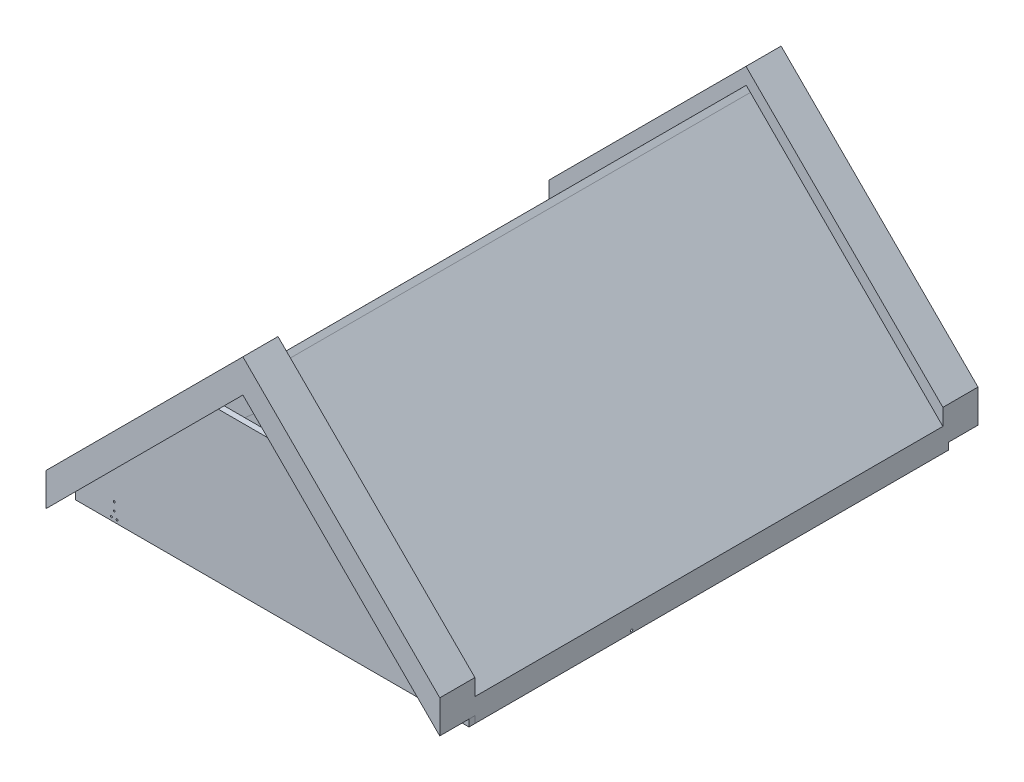
SolidWorks part; units mm, degrees
material "Pine"
ref_plane "Front Plane" through (0, 0, 0) normal (0, 0, 1) x (1, 0, 0)
ref_plane "Top Plane" through (0, 0, 0) normal (0, 1, 0) x (1, 0, 0)
ref_plane "Right Plane" through (0, 0, 0) normal (1, 0, 0) x (0, 0, -1)
sketch "Sketch1" plane through (0, 0, 0) normal (0, 0, 1) x (1, 0, 0)
  line L0 (0, 0) -> (1400, 0)
  line L1 (700, 0) -> (700, 700)
  line L2 (700, 700) -> (0, 0)
  line L3 (700, 700) -> (1400, 0)
  dimension "D1" = 1400
  dimension "D2" = 700
extrude "Boss-Extrude1" add sketch "Sketch1" along normal blind 2000 contours L3 L0 L2
shell "Shell1" thickness 10 removed face at (700, 0, 1000)
sketch "Sketch2" plane through (0, 0, 0) normal (0, -1, 0) x (1, 0, 0)
  line L0 (0, 2000) -> (1400, 2000) construction
  line L1 (-150, 2150) -> (1550, 2150)
  line L2 (-150, 2150) -> (-150, -150)
  line L3 (-150, -150) -> (1550, -150)
  line L4 (1550, 2150) -> (1550, -150)
  line L5 (0, 2000) -> (0, 0) construction
  dimension "D1" = 1700
  dimension "D2" = 2300
  dimension "D3" = 150
  dimension "D4" = 150
sketch "Sketch3" plane through (0, 0, 0) normal (-0.7071, 0.7071, 0) x (0, 0, 1)
  line L10 (2150, 1096.0155) -> (2000, 1096.0155)
  line L11 (2150, 1096.0155) -> (2150, 0)
  line L12 (2150, 0) -> (2000, 0)
  line L13 (2000, 1096.0155) -> (2000, 0)
extrude "Boss-Extrude2" add sketch "Sketch3" along normal blind 100 separate body contours L11 L10 L13 L12
sketch "Sketch7" plane through (700, 700, 0) normal (0.7071, 0.7071, 0) x (0, 0, -1)
  line L5 (-2150, 100) -> (-2000, 100)
  line L6 (-2150, 100) -> (-2150, -989.9495)
  line L7 (-2150, -989.9495) -> (-2000, -989.9495)
  line L8 (-2000, 100) -> (-2000, -989.9495)
extrude "Boss-Extrude4" add sketch "Sketch7" along normal blind 100
sketch "Sketch8" plane through (775, 775, 0) normal (0.7071, 0.7071, 0) x (0, 0, -1)
  line L1 (-2000, 100) -> (-2150, 100)
  line L2 (-2000, 100) -> (-2000, 0)
  line L3 (-2000, 0) -> (-2150, 0)
  line L4 (-2150, 100) -> (-2150, 0)
extrude "Cut-Extrude1" cut sketch "Sketch8" against normal up to vertex (6.066 mm away) and the other way blind 6 up to point (770.7107, 770.7107, 2150)
sketch "Sketch9" plane through (0, 0, 0) normal (-0.7071, -0.7071, 0) x (0, 0, 1)
  line L2 (2000, 100) -> (2150, 100)
  line L3 (2000, 100) -> (2000, 0)
  line L4 (2000, 0) -> (2150, 0)
  line L5 (2150, 100) -> (2150, 0)
extrude "Boss-Extrude5" add sketch "Sketch9" along normal blind 239.05
sketch "Sketch10" plane through (700, -700, 0) normal (0.7071, -0.7071, 0) x (0, 0, -1)
  line L1 (-2000, 989.9495) -> (-2150, 989.9495)
  line L2 (-2000, 989.9495) -> (-2000, 1089.9495)
  line L3 (-2000, 1089.9495) -> (-2150, 1089.9495)
  line L4 (-2150, 989.9495) -> (-2150, 1089.9495)
extrude "Boss-Extrude6" add sketch "Sketch10" along normal blind 399.5
sketch "Sketch13" plane through (0, 0, 2150) normal (0, 0, 1) x (1, 0, 0)
  line L0 (-141.4214, 0) -> (-141.4214, -141.4214)
  line L1 (-150, 0) -> (1550, 0) construction
  line L2 (700, 841.4214) -> (-239.7446, -98.3232) construction
  line L3 (700, 700) -> (-169.0339, -169.0339) construction
  line L4 (-141.4214, -141.4214) -> (-169.0339, -169.0339)
  line L5 (-169.0339, -169.0339) -> (-239.7446, -98.3232)
  line L6 (-239.7446, -98.3232) -> (-141.4214, 0)
  line L7 (1541.4214, 0) -> (1753.1998, -211.7785)
  line L8 (700, 841.4214) -> (1753.1998, -211.7785) construction
  line L9 (1753.1998, -211.7785) -> (1682.4892, -282.4892)
  line L10 (1682.4892, -282.4892) -> (1541.2446, -141.2446)
  line L12 (1541.4214, 0) -> (1541.2446, -141.2446)
extrude "Cut-Extrude4" cut sketch "Sketch13" against normal blind 1197.5
ref_plane "Plane1" through (0, 0, 1000) normal (0, 0, 1) x (1, 0, 0)
mirror "Mirror4" about plane through (0, 0, 1000) normal (0, 0, 1) of bodies 114 108
sketch "Sketch14" plane through (-141.4214, 0, 0) normal (-1, 0, 0) x (0, 0, 1)
  line L0 (0, -141.4214) -> (0, 0) construction
  line L5 (0, -70.7107) -> (2000, -70.7107)
  line L6 (0, -70.7107) -> (0, -170.7107)
  line L7 (0, -170.7107) -> (2000, -170.7107)
  line L8 (2000, -70.7107) -> (2000, -170.7107)
  dimension "D1" = 100
  dimension "D2" = 70.7107
  dimension "D3" = 2000
extrude "Boss-Extrude7" add sketch "Sketch14" against normal blind 25
sketch "Sketch15" plane through (1541.4189, -1.9292, 0) normal (1, -0.0013, 0) x (0, 0, -1)
  line L0 (-2000, 1.9292) -> (-2000, -139.3155) construction
  line L2 (-2000, -68.6932) -> (-2000, -70.8563)
  line L4 (0, -68.6932) -> (0, -70.8563)
  line L6 (-2000, -68.6932) -> (0, -68.6932)
  line L7 (-2000, -68.6932) -> (-2000, -168.6932)
  line L8 (-2000, -168.6932) -> (0, -168.6932)
  line L9 (0, -68.6932) -> (0, -168.6932)
  dimension "D1" = 100
extrude "Boss-Extrude8" add sketch "Sketch15" against normal blind 25 contours L7 L6 L9 L8
ref_plane "Plane2" through (-106.066, -106.066, 0) normal (0.7071, 0.7071, 0) x (0, 0, -1)
sketch "Sketch16" plane through (-106.066, -106.066, 0) normal (0.7071, 0.7071, 0) x (0, 0, -1)
  line L0 (0, -1089.9495) -> (0, 100) construction
  line L1 (-2000, 50) -> (0, 50)
  line L2 (-2000, 50) -> (-2000, 25)
  line L3 (-2000, 25) -> (0, 25)
  line L4 (0, 50) -> (0, 25)
  line L5 (-2000, 50) -> (0, 50) construction
  dimension "D1" = 25
  dimension "D2" = 2000
extrude "Boss-Extrude9" add sketch "Sketch16" along normal blind 1436
ref_plane "Plane3" through (804.0484, -806.0636, 0) normal (-0.7062, 0.708, 0) x (0.708, 0.7062, 0)
sketch "Sketch17" plane through (804.0484, -806.0636, 0) normal (-0.7062, 0.708, 0) x (0.708, 0.7062, 0)
  line L0 (1091.3128, 0) -> (1089.9174, 0) construction
  line L1 (1041.3752, 0) -> (1016.3752, 0)
  line L2 (1041.3752, 0) -> (1041.3752, -2000)
  line L3 (1041.3752, -2000) -> (1016.3752, -2000)
  line L4 (1016.3752, 0) -> (1016.3752, -2000)
  dimension "D1" = 25
  dimension "D2" = 2000
extrude "Boss-Extrude10" add sketch "Sketch17" along normal blind 1436
sketch "Sketch25" plane through (-35.3553, 35.3553, 0) normal (-0.7071, 0.7071, 0) x (0, 0, 1)
  line L6 (0, 1041.4386) -> (2000, 1041.4386)
  line L7 (2000, 1041.4386) -> (2000, 1089.9495)
  line L8 (2000, 1089.9495) -> (2000, 1286)
  line L9 (2000, 1286) -> (0, 1286)
  line L10 (0, 1286) -> (0, 1089.9495)
  line L11 (0, 1089.9495) -> (0, 1041.4386)
  line L12 (0, 1041.4386) -> (2000, 1041.4386)
  line L13 (2000, 1041.4386) -> (2000, 1089.9495)
  line L14 (2000, 1089.9495) -> (2000, 1286)
  line L15 (2000, 1286) -> (0, 1286)
  line L16 (0, 1286) -> (0, 1089.9495)
  line L17 (0, 1089.9495) -> (0, 1041.4386)
  dimension "D1" = 0
sketch "Sketch26" plane through (737.2845, 735.4413, 0) normal (0.708, 0.7062, 0) x (0, 0, -1)
  line L6 (-2000, 101.3034) -> (-2000, 51.3034)
  line L7 (-2000, 51.3034) -> (0, 51.3034)
  line L8 (0, 51.3034) -> (0, 101.3034)
  line L9 (0, 101.3034) -> (0, 297.478)
  line L10 (0, 297.478) -> (-2000, 297.478)
  line L11 (-2000, 297.478) -> (-2000, 101.3034)
  line L12 (-2000, 101.3034) -> (-2000, 51.3034)
  line L14 (0, 51.3034) -> (0, 101.3034)
  line L15 (0, 101.3034) -> (0, 297.478)
  line L16 (0, 297.478) -> (-2000, 297.478)
  line L17 (-2000, 297.478) -> (-2000, 101.3034)
  line L18 (-2000, 51.3034) -> (0, 51.3034)
  dimension "D1" = 0
sketch "Sketch27" plane through (719.5847, 717.7858, 0) normal (-0.708, -0.7062, 0) x (0, 0, 1)
  line L6 (0, 101.2721) -> (0, 51.2721)
  line L7 (0, 51.2721) -> (2000, 51.2721)
  line L8 (2000, 51.2721) -> (2000, 101.2721)
  line L9 (2000, 101.2721) -> (2000, 297.478)
  line L10 (2000, 297.478) -> (0, 297.478)
  line L11 (0, 297.478) -> (0, 101.2721)
  line L12 (0, 101.2721) -> (0, 51.2721)
  line L13 (0, 51.2721) -> (2000, 51.2721)
  line L14 (2000, 51.2721) -> (2000, 101.2721)
  line L15 (2000, 101.2721) -> (2000, 297.478)
  line L16 (2000, 297.478) -> (0, 297.478)
  line L17 (0, 297.478) -> (0, 101.2721)
  dimension "D1" = 0
extrude "Cut-Extrude11" cut sketch "Sketch27" against normal blind 1286
sketch "Sketch28" plane through (-17.6777, 17.6777, 0) normal (0.7071, -0.7071, 0) x (0, 0, -1)
  line L6 (-2000, 1041.4073) -> (0, 1041.4073)
  line L7 (0, 1041.4073) -> (0, 1089.9495)
  line L8 (0, 1089.9495) -> (0, 1286)
  line L9 (0, 1286) -> (-2000, 1286)
  line L10 (-2000, 1286) -> (-2000, 1089.9495)
  line L11 (-2000, 1089.9495) -> (-2000, 1041.4073)
  line L12 (-2000, 1041.4073) -> (0, 1041.4073)
  line L13 (0, 1041.4073) -> (0, 1089.9495)
  line L14 (0, 1089.9495) -> (0, 1286)
  line L15 (0, 1286) -> (-2000, 1286)
  line L16 (-2000, 1286) -> (-2000, 1089.9495)
  line L17 (-2000, 1089.9495) -> (-2000, 1041.4073)
  dimension "D1" = 0
extrude "Cut-Extrude12" cut sketch "Sketch28" against normal blind 1286
sketch "Sketch29" plane through (0, 0, 2000) normal (0, 0, -1) x (-1, 0, 0)
  line L1 (-701.0308, 594.9648) -> (-1466.5902, -170.5946)
  line L2 (-630.3202, 665.6755) -> (116.4214, -81.066)
  line L4 (-701.0308, 594.9648) -> (64.6409, -170.7069)
  line L5 (116.4214, -170.7107) -> (64.6409, -170.7069)
  line L6 (116.4214, -81.066) -> (-701.0308, 736.3862)
  line L7 (-701.0308, 736.3862) -> (-1516.32, -80.9463)
  line L8 (-1516.32, -80.9463) -> (-1516.2758, -116.2758)
  line L9 (-1516.2758, -116.2758) -> (-700, 700)
  line L10 (-700, 700) -> (116.4214, -116.4214)
  line L11 (116.4214, -116.4214) -> (116.4214, -81.066)
  line L12 (-630.3202, 665.6755) -> (-701.0308, 736.3862)
  line L13 (-701.0308, 736.3862) -> (-1516.32, -80.9463)
  line L18 (-1466.5902, -170.5946) -> (-1516.2078, -170.5909)
  line L19 (-1516.32, -80.9463) -> (-1516.2078, -170.5909)
  line L20 (116.4214, -81.066) -> (116.4214, -170.7107)
  dimension "D2" = 100
  dimension "D3" = 100
  dimension "D1" = 0
extrude "Boss-Extrude13" add sketch "Sketch29" along normal blind 50
ref_plane "Plane4" through (0, 0, 1359) normal (0, 0, -1) x (-1, 0, 0)
sketch "Sketch30" plane through (0, 0, 1359) normal (0, 0, -1) x (-1, 0, 0)
  line L8 (-701.0308, 736.3862) -> (-1516.32, -80.9463)
  line L9 (-701.0308, 736.3862) -> (-1516.32, -80.9463)
  line L10 (-1516.2078, -170.5909) -> (-1466.5902, -170.5946)
  line L11 (-1466.5902, -170.5946) -> (-701.0308, 594.9648)
  line L12 (-701.0308, 594.9648) -> (64.6409, -170.7069)
  line L13 (64.6409, -170.7069) -> (116.4214, -170.7107)
  line L14 (-1516.32, -80.9463) -> (-1516.2078, -170.5909)
  line L15 (-1516.32, -80.9463) -> (-1516.2078, -170.5909)
  line L18 (-1516.2078, -170.5909) -> (-1466.5902, -170.5946)
  line L19 (-1466.5902, -170.5946) -> (-701.0308, 594.9648)
  line L20 (-701.0308, 594.9648) -> (64.6409, -170.7069)
  line L21 (64.6409, -170.7069) -> (116.4214, -170.7107)
  line L24 (116.4214, -170.7107) -> (116.4214, -81.066)
  line L25 (116.4214, -170.7107) -> (116.4214, -81.066)
  line L26 (116.4214, -81.066) -> (-701.0308, 736.3862)
  line L27 (116.4214, -81.066) -> (-701.0308, 736.3862)
  dimension "D1" = 0
extrude "Boss-Extrude14" add sketch "Sketch30" along normal blind 50
ref_plane "Plane5" through (0, 0, 691) normal (0, 0, -1) x (-1, 0, 0)
sketch "Sketch31" plane through (0, 0, 691) normal (0, 0, -1) x (-1, 0, 0)
  line L8 (116.4214, -81.066) -> (-701.0308, 736.3862)
  line L9 (-701.0308, 736.3862) -> (-1516.32, -80.9463)
  line L10 (-1516.32, -80.9463) -> (-1516.2078, -170.5909)
  line L11 (-1516.2078, -170.5909) -> (-1466.5902, -170.5946)
  line L12 (-1466.5902, -170.5946) -> (-701.0308, 594.9648)
  line L13 (-701.0308, 594.9648) -> (64.6409, -170.7069)
  line L14 (64.6409, -170.7069) -> (116.4214, -170.7107)
  line L15 (116.4214, -170.7107) -> (116.4214, -81.066)
  line L16 (116.4214, -81.066) -> (-701.0308, 736.3862)
  line L17 (-701.0308, 736.3862) -> (-1516.32, -80.9463)
  line L18 (-1516.32, -80.9463) -> (-1516.2078, -170.5909)
  line L19 (-1516.2078, -170.5909) -> (-1466.5902, -170.5946)
  line L20 (-1466.5902, -170.5946) -> (-701.0308, 594.9648)
  line L21 (-701.0308, 594.9648) -> (64.6409, -170.7069)
  line L22 (64.6409, -170.7069) -> (116.4214, -170.7107)
  line L23 (116.4214, -170.7107) -> (116.4214, -81.066)
  dimension "D1" = 0
extrude "Boss-Extrude15" add sketch "Sketch31" along normal blind 50
ref_plane "Plane6" through (0, 0, 50) normal (0, 0, -1) x (-1, 0, 0)
sketch "Sketch33" plane through (0, 0, 50) normal (0, 0, -1) x (-1, 0, 0)
  line L8 (116.4214, -170.7107) -> (116.4214, -81.066)
  line L9 (116.4214, -81.066) -> (-701.0308, 736.3862)
  line L10 (-701.0308, 736.3862) -> (-1516.32, -80.9463)
  line L11 (-1516.32, -80.9463) -> (-1516.2078, -170.5909)
  line L12 (-1516.2078, -170.5909) -> (-1466.5902, -170.5946)
  line L13 (-1466.5902, -170.5946) -> (-701.0308, 594.9648)
  line L14 (-701.0308, 594.9648) -> (64.6409, -170.7069)
  line L15 (64.6409, -170.7069) -> (116.4214, -170.7107)
  line L16 (116.4214, -170.7107) -> (116.4214, -81.066)
  line L17 (116.4214, -81.066) -> (-701.0308, 736.3862)
  line L18 (-701.0308, 736.3862) -> (-1516.32, -80.9463)
  line L19 (-1516.32, -80.9463) -> (-1516.2078, -170.5909)
  line L20 (-1516.2078, -170.5909) -> (-1466.5902, -170.5946)
  line L21 (-1466.5902, -170.5946) -> (-701.0308, 594.9648)
  line L22 (-701.0308, 594.9648) -> (64.6409, -170.7069)
  line L23 (64.6409, -170.7069) -> (116.4214, -170.7107)
  dimension "D1" = 0
extrude "Boss-Extrude16" add sketch "Sketch33" along normal blind 50
sketch "Sketch35" plane through (0, 0, 2000) normal (0, 0, 1) x (1, 0, 0)
  line L0 (60.3572, -45.7088) -> (1341.7044, -45.7088)
  line L1 (701.0308, 594.9648) -> (-64.6409, -170.7069) construction
  line L2 (-39.6428, -145.7088) -> (1441.7044, -145.7088)
  line L3 (1466.5902, -170.5946) -> (701.0308, 594.9648) construction
  line L4 (60.3572, -45.7088) -> (-39.6428, -145.7088)
  line L5 (1341.7044, -45.7088) -> (1441.7044, -145.7088)
  line L9 (-64.6409, -170.7069) -> (-116.4214, -170.7107) construction
  line L10 (-64.6409, -170.7069) -> (-116.4214, -170.7107)
  point P10 (-90.5311, -170.7088)
  line M8 (-64.6409, -170.7069) -> (701.0308, 594.9648)
  line M9 (701.0308, 594.9648) -> (1466.5902, -170.5946)
  dimension "D1" = 100
  dimension "D2" = 25
extrude "Boss-Extrude17" add sketch "Sketch35" against normal blind 50 separate body contours L2 L0 M8 M9 region at (701.0308, -96.9153, 2000)
sketch "Sketch36" plane through (0, 0, 1359) normal (0, 0, -1) x (-1, 0, 0)
  line L4 (39.6428, -145.7088) -> (-60.3572, -45.7088)
  line L5 (-60.3572, -45.7088) -> (-1341.7044, -45.7088)
  line L6 (-1341.7044, -45.7088) -> (-1441.7044, -145.7088)
  line L7 (-1441.7044, -145.7088) -> (39.6428, -145.7088)
  line L8 (39.6428, -145.7088) -> (-60.3572, -45.7088)
  line L9 (-60.3572, -45.7088) -> (-1341.7044, -45.7088)
  line L10 (-1341.7044, -45.7088) -> (-1441.7044, -145.7088)
  line L11 (-1441.7044, -145.7088) -> (39.6428, -145.7088)
  dimension "D1" = 0
extrude "Boss-Extrude18" add sketch "Sketch36" along normal blind 50 separate body
sketch "Sketch37" plane through (0, 0, 691) normal (0, 0, -1) x (-1, 0, 0)
  line L4 (-1441.7044, -145.7088) -> (39.6428, -145.7088)
  line L5 (39.6428, -145.7088) -> (-60.3572, -45.7088)
  line L6 (-60.3572, -45.7088) -> (-1341.7044, -45.7088)
  line L7 (-1341.7044, -45.7088) -> (-1441.7044, -145.7088)
  line L8 (-1441.7044, -145.7088) -> (39.6428, -145.7088)
  line L9 (39.6428, -145.7088) -> (-60.3572, -45.7088)
  line L10 (-60.3572, -45.7088) -> (-1341.7044, -45.7088)
  line L11 (-1341.7044, -45.7088) -> (-1441.7044, -145.7088)
  dimension "D1" = 0
extrude "Boss-Extrude19" add sketch "Sketch37" along normal blind 50 separate body
sketch "Sketch38" plane through (0, 0, 50) normal (0, 0, -1) x (-1, 0, 0)
  line L4 (-1341.7044, -45.7088) -> (-1441.7044, -145.7088)
  line L5 (-1441.7044, -145.7088) -> (39.6428, -145.7088)
  line L6 (39.6428, -145.7088) -> (-60.3572, -45.7088)
  line L7 (-60.3572, -45.7088) -> (-1341.7044, -45.7088)
  line L8 (-1341.7044, -45.7088) -> (-1441.7044, -145.7088)
  line L9 (-1441.7044, -145.7088) -> (39.6428, -145.7088)
  line L10 (39.6428, -145.7088) -> (-60.3572, -45.7088)
  line L11 (-60.3572, -45.7088) -> (-1341.7044, -45.7088)
  dimension "D1" = 0
extrude "Boss-Extrude20" add sketch "Sketch38" along normal blind 50 separate body
sketch "Sketch34" plane through (0.0125, -170.7021, 0) normal (0.0001, -1, 0) x (1, 0.0001, 0)
  line L0 (1441.6938, 1950) -> (1441.6938, 2000) construction
  line L5 (1.0188, 2000) -> (1401.0188, 2000)
  line L6 (1.0188, 2000) -> (1.0188, 0)
  line L7 (1.0188, 0) -> (1401.0188, 0)
  line L8 (1401.0188, 2000) -> (1401.0188, 0)
  line L9 (-39.6534, 2000) -> (1441.6938, 2000) construction
  dimension "D1" = 1400
  dimension "D2" = 2000
  dimension "D3" = 40.675
extrude "Boss-Extrude21" add sketch "Sketch34" against normal blind 25 separate body
sketch "Sketch39" plane through (0, 0, 2000) normal (0, 0, 1) x (1, 0, 0)
  line L0 (-64.6409, -170.7069) -> (1466.5902, -170.5946)
  line L1 (470, 470) -> (930, 470)
  line L10 (-141.4214, -170.7107) -> (-116.4214, -170.7107)
  line L11 (-116.4214, -170.7107) -> (-64.6409, -170.7069)
  line L12 (-64.6409, -170.7069) -> (701.0308, 594.9648)
  line L13 (701.0308, 594.9648) -> (1466.5902, -170.5946)
  line L14 (1466.5902, -170.5946) -> (1516.2078, -170.5909)
  line L15 (1516.2078, -170.5909) -> (1541.2078, -170.6222)
  line L16 (1541.2078, -170.6222) -> (1541.2446, -141.2446)
  line L17 (1541.2446, -141.2446) -> (700, 700)
  line L18 (700, 700) -> (-141.4214, -141.4214)
  line L19 (-141.4214, -141.4214) -> (-141.4214, -170.7107)
  line L20 (-141.4214, -170.7107) -> (-116.4214, -170.7107)
  line L21 (-116.4214, -170.7107) -> (-64.6409, -170.7069)
  line L24 (1466.5902, -170.5946) -> (1516.2078, -170.5909)
  line L25 (1516.2078, -170.5909) -> (1541.2078, -170.6222)
  line L26 (1541.2078, -170.6222) -> (1541.2446, -141.2446)
  line L27 (1541.2446, -141.2446) -> (930, 470)
  line L28 (470, 470) -> (-141.4214, -141.4214)
  line L29 (-141.4214, -141.4214) -> (-141.4214, -170.7107)
  dimension "D2" = 460
  dimension "D1" = 0
extrude "Boss-Extrude22" add sketch "Sketch39" along normal blind 25 separate body
sketch "Sketch40" plane through (0, 0, 0) normal (0, 0, -1) x (-1, 0, 0)
  line L0 (-1466.5902, -170.5946) -> (64.6409, -170.7069)
  line L2 (-930, 470) -> (-470, 470)
  line L10 (141.4214, -170.7107) -> (141.4214, -141.4214)
  line L11 (141.4214, -141.4214) -> (-700, 700)
  line L12 (-700, 700) -> (-1541.2446, -141.2446)
  line L13 (-1541.2446, -141.2446) -> (-1541.2078, -170.6222)
  line L14 (-1541.2078, -170.6222) -> (-1516.2078, -170.5909)
  line L15 (-1516.2078, -170.5909) -> (-1466.5902, -170.5946)
  line L16 (-1466.5902, -170.5946) -> (-701.0308, 594.9648)
  line L17 (-701.0308, 594.9648) -> (64.6409, -170.7069)
  line L18 (64.6409, -170.7069) -> (116.4214, -170.7107)
  line L19 (116.4214, -170.7107) -> (141.4214, -170.7107)
  line L20 (141.4214, -170.7107) -> (141.4214, -141.4214)
  line L21 (141.4214, -141.4214) -> (-470, 470)
  line L22 (-930, 470) -> (-1541.2446, -141.2446)
  line L23 (-1541.2446, -141.2446) -> (-1541.2078, -170.6222)
  line L24 (-1541.2078, -170.6222) -> (-1516.2078, -170.5909)
  line L25 (-1516.2078, -170.5909) -> (-1466.5902, -170.5946)
  line L28 (64.6409, -170.7069) -> (116.4214, -170.7107)
  line L29 (116.4214, -170.7107) -> (141.4214, -170.7107)
  dimension "D2" = 460
  dimension "D1" = 0
extrude "Boss-Extrude23" add sketch "Sketch40" along normal blind 25
sketch "Sketch41" plane through (0.0125, -170.7021, 0) normal (0.0001, -1, 0) x (1, 0.0001, 0)
  line L0 (12.3035, 1864.4107) -> (16.9035, 1864.4244)
  line L1 (1.0015, 1999.9778) -> (12.3035, 1864.4107)
  line L2 (0.9765, 2008.4278) -> (1.0015, 1999.9778)
  line L3 (9.9764, 2008.4544) -> (0.9765, 2008.4278)
  line L4 (10.0015, 2000.0045) -> (9.9764, 2008.4544)
  line L5 (27.8014, 2000.0573) -> (10.0015, 2000.0045)
  line L6 (27.7764, 2008.5072) -> (27.8014, 2000.0573)
  line L7 (36.7763, 2008.5339) -> (27.7764, 2008.5072)
  line L8 (36.8014, 2000.084) -> (36.7763, 2008.5339)
  line L9 (26.3034, 1864.4523) -> (36.8014, 2000.084)
  line L10 (21.7034, 1864.4386) -> (26.3034, 1864.4523)
  line L77 (1376.4806, 1864.3486) -> (1381.0806, 1864.3622)
  line L78 (1365.1787, 1999.9157) -> (1376.4806, 1864.3486)
  line L79 (1365.1536, 2008.3656) -> (1365.1787, 1999.9157)
  line L80 (1374.1536, 2008.3923) -> (1365.1536, 2008.3656)
  line L81 (1374.1786, 1999.9423) -> (1374.1536, 2008.3923)
  line L82 (1391.9786, 1999.9951) -> (1374.1786, 1999.9423)
  line L83 (1391.9535, 2008.445) -> (1391.9786, 1999.9951)
  line L84 (1400.9535, 2008.4717) -> (1391.9535, 2008.445)
  line L85 (1400.9785, 2000.0218) -> (1400.9535, 2008.4717)
  line L86 (1390.4806, 1864.3901) -> (1400.9785, 2000.0218)
  line L87 (1385.8806, 1864.3764) -> (1390.4806, 1864.3901)
  spline S0 degree 3 poles (27.8669, 1977.9724) (22.8369, 1977.9575) (22.8518, 1972.9275) (27.8818, 1972.9424) (32.9118, 1972.9573) (32.8969, 1977.9873) (27.8669, 1977.9724) (22.8369, 1977.9575) (22.8518, 1972.9275) knots -0.5 0 0 0 0.5 0.5 0.5 1 1 1 1.5 1.5 1.5 weights 1 0.333333 0.333333 1 0.333333 0.333333 1 0.333333 0.333333 only from (27.8669, 1977.9724) to (27.8669, 1977.9724)
  spline S1 degree 3 poles (19.1096, 1929.8312) (14.3096, 1929.817) (14.3238, 1925.017) (19.1238, 1925.0312) (23.9238, 1925.0455) (23.9095, 1929.8454) (19.1096, 1929.8312) (14.3096, 1929.817) (14.3238, 1925.017) knots -0.5 0 0 0 0.5 0.5 0.5 1 1 1 1.5 1.5 1.5 weights 1 0.333333 0.333333 1 0.333333 0.333333 1 0.333333 0.333333 only from (19.1096, 1929.8312) to (19.1096, 1929.8312)
  spline S32 degree 3 poles (19.2519, 1881.8314) (14.4519, 1881.8172) (14.4661, 1877.0172) (19.2661, 1877.0314) (24.0661, 1877.0457) (24.0518, 1881.8457) (19.2519, 1881.8314) (14.4519, 1881.8172) (14.4661, 1877.0172) knots -0.5 0 0 0 0.5 0.5 0.5 1 1 1 1.5 1.5 1.5 weights 1 0.333333 0.333333 1 0.333333 0.333333 1 0.333333 0.333333 only from (19.2519, 1881.8314) to (19.2519, 1881.8314)
  spline S33 degree 3 poles (10.0366, 1988.1686) (4.5086, 1988.1522) (4.525, 1982.6242) (10.053, 1982.6406) (15.581, 1982.657) (15.5646, 1988.185) (10.0366, 1988.1686) (4.5086, 1988.1522) (4.525, 1982.6242) knots -0.5 0 0 0 0.5 0.5 0.5 1 1 1 1.5 1.5 1.5 weights 1 0.333333 0.333333 1 0.333333 0.333333 1 0.333333 0.333333 only from (10.0366, 1988.1686) to (10.0366, 1988.1686)
  spline S34 degree 3 poles (16.9035, 1864.4244) (16.9177, 1859.6244) (21.7177, 1859.6386) (21.7034, 1864.4386) knots 0 0 0 0 1 1 1 1 weights 1 0.333333 0.333333 1
  spline S35 degree 3 poles (1392.044, 1977.9102) (1387.014, 1977.8953) (1387.029, 1972.8653) (1392.0589, 1972.8802) (1397.0889, 1972.8951) (1397.074, 1977.9251) (1392.044, 1977.9102) (1387.014, 1977.8953) (1387.029, 1972.8653) knots -0.5 0 0 0 0.5 0.5 0.5 1 1 1 1.5 1.5 1.5 weights 1 0.333333 0.333333 1 0.333333 0.333333 1 0.333333 0.333333 only from (1392.044, 1977.9102) to (1392.044, 1977.9102)
  spline S36 degree 3 poles (1383.2867, 1929.769) (1378.4867, 1929.7548) (1378.501, 1924.9548) (1383.3009, 1924.969) (1388.1009, 1924.9833) (1388.0867, 1929.7833) (1383.2867, 1929.769) (1378.4867, 1929.7548) (1378.501, 1924.9548) knots -0.5 0 0 0 0.5 0.5 0.5 1 1 1 1.5 1.5 1.5 weights 1 0.333333 0.333333 1 0.333333 0.333333 1 0.333333 0.333333 only from (1383.2867, 1929.769) to (1383.2867, 1929.769)
  spline S37 degree 3 poles (1383.429, 1881.7692) (1378.629, 1881.755) (1378.6433, 1876.955) (1383.4432, 1876.9693) (1388.2432, 1876.9835) (1388.229, 1881.7835) (1383.429, 1881.7692) (1378.629, 1881.755) (1378.6433, 1876.955) knots -0.5 0 0 0 0.5 0.5 0.5 1 1 1 1.5 1.5 1.5 weights 1 0.333333 0.333333 1 0.333333 0.333333 1 0.333333 0.333333 only from (1383.429, 1881.7692) to (1383.429, 1881.7692)
  spline S38 degree 3 poles (1374.2137, 1988.1064) (1368.6857, 1988.09) (1368.7021, 1982.562) (1374.2301, 1982.5784) (1379.7581, 1982.5948) (1379.7417, 1988.1228) (1374.2137, 1988.1064) (1368.6857, 1988.09) (1368.7021, 1982.562) knots -0.5 0 0 0 0.5 0.5 0.5 1 1 1 1.5 1.5 1.5 weights 1 0.333333 0.333333 1 0.333333 0.333333 1 0.333333 0.333333 only from (1374.2137, 1988.1064) to (1374.2137, 1988.1064)
  spline S39 degree 3 poles (1381.0806, 1864.3622) (1381.0948, 1859.5622) (1385.8948, 1859.5764) (1385.8806, 1864.3764) knots 0 0 0 0 1 1 1 1 weights 1 0.333333 0.333333 1
extrude "Cut-Extrude14" [suppressed] cut sketch "Sketch41" against normal blind 10 contours S33 | S0 | S1 | S36 | S35 | S38
ref_plane "Plane7" through (0, 0, 2010) normal (0, 0, 1) x (1, 0, 0)
sketch "Sketch42" plane through (0, 0, 2010) normal (0, 0, 1) x (-1, 0, 0)
  line L88 (-1349.3821, 25.2633) -> (-1353.982, 25.2497)
  line L89 (-1353.982, 25.2497) -> (-1362.944, 132.749)
  line L90 (-1362.944, 132.749) -> (-1363.0523, 169.2734)
  line L91 (-1363.0523, 169.2734) -> (-1356.3091, 169.2934)
  line L92 (-1356.3091, 169.2934) -> (-1356.284, 160.8434)
  line L93 (-1356.284, 160.8434) -> (-1338.5085, 160.8961)
  line L94 (-1338.5085, 160.8961) -> (-1338.5336, 169.3595)
  line L95 (-1331.5821, 133.8178) -> (-1339.9821, 25.2912)
  line L96 (-1339.9821, 25.2912) -> (-1344.5821, 25.2775)
  line L97 (-1331.5821, 133.8178) -> (-1331.7903, 169.3595)
  line L99 (-1331.7903, 169.3595) -> (-1338.5336, 169.3595)
  spline S2 degree 3 poles (-1344.5821, 25.2775) (-1344.5679, 20.4775) (-1349.3678, 20.4633) (-1349.3821, 25.2633) knots 0 0 0 0 1 1 1 1 weights 1 0.333333 0.333333 1
  spline S3 degree 3 poles (-1338.449, 149.0603) (-1332.921, 149.0766) (-1332.9047, 143.5487) (-1338.4326, 143.5323) (-1343.9606, 143.5159) (-1343.977, 149.0439) (-1338.449, 149.0603) (-1332.921, 149.0766) (-1332.9047, 143.5487) knots -0.5 0 0 0 0.5 0.5 0.5 1 1 1 1.5 1.5 1.5 weights 1 0.333333 0.333333 1 0.333333 0.333333 1 0.333333 0.333333 only from (-1338.449, 149.0603) to (-1338.449, 149.0603)
  spline S4 degree 3 poles (-1347.0337, 42.6703) (-1342.2337, 42.6846) (-1342.2194, 37.8846) (-1347.0194, 37.8704) (-1351.8194, 37.8561) (-1351.8336, 42.6561) (-1347.0337, 42.6703) (-1342.2337, 42.6846) (-1342.2194, 37.8846) knots -0.5 0 0 0 0.5 0.5 0.5 1 1 1 1.5 1.5 1.5 weights 1 0.333333 0.333333 1 0.333333 0.333333 1 0.333333 0.333333 only from (-1347.0337, 42.6703) to (-1347.0337, 42.6703)
  spline S5 degree 3 poles (-1347.176, 90.6701) (-1342.376, 90.6844) (-1342.3617, 85.8844) (-1347.1617, 85.8701) (-1351.9617, 85.8559) (-1351.9759, 90.6559) (-1347.176, 90.6701) (-1342.376, 90.6844) (-1342.3617, 85.8844) knots -0.5 0 0 0 0.5 0.5 0.5 1 1 1 1.5 1.5 1.5 weights 1 0.333333 0.333333 1 0.333333 0.333333 1 0.333333 0.333333 only from (-1347.176, 90.6701) to (-1347.176, 90.6701)
  spline S6 degree 3 poles (-1356.2186, 138.7585) (-1351.1886, 138.7734) (-1351.1737, 133.7435) (-1356.2036, 133.7285) (-1361.2336, 133.7136) (-1361.2485, 138.7436) (-1356.2186, 138.7585) (-1351.1886, 138.7734) (-1351.1737, 133.7435) knots -0.5 0 0 0 0.5 0.5 0.5 1 1 1 1.5 1.5 1.5 weights 1 0.333333 0.333333 1 0.333333 0.333333 1 0.333333 0.333333 only from (-1356.2186, 138.7585) to (-1356.2186, 138.7585)
  dimension "D1" = 1331.5821
  dimension "D2" = 1331.7903
  dimension "D3" = 1338.449
  dimension "D4" = 1338.5085
  dimension "D5" = 1338.5336
  dimension "D6" = 1339.9821
  dimension "D7" = 1344.5821
  dimension "D8" = 1347.0337
  dimension "D9" = 1347.176
  dimension "D10" = 1349.3821
  dimension "D11" = 1356.3091
  dimension "D12" = 1356.2186
  dimension "D13" = 1356.284
  dimension "D14" = 1363.0523
  dimension "D15" = 1362.944
  dimension "D16" = 25.2497
  dimension "D17" = 132.749
  dimension "D18" = 149.0603
  dimension "D20" = 42.6703
  dimension "D21" = 90.6701
  dimension "D23" = 133.8178
extrude "Cut-Extrude15" [suppressed] cut sketch "Sketch42" against normal blind 20
sketch "Sketch43" plane through (0, 0, 0) normal (1, 0, 0) x (0, 0, -1)
  line L0 (-2000, -170.6222) -> (25, -170.6222) construction
  line L1 (-2150, 0) -> (-2150, -141.2446) construction
  circle A0 centre (-1330, -160.6222) radius 5
  dimension "D1" = 10
  dimension "D2" = 10
  dimension "D3" = 820
extrude "Cut-Extrude16" cut sketch "Sketch43" against normal through all both and the other way through all
sketch "Sketch45" plane through (0, 0, 2000) normal (0, 0, 1) x (1, 0, 0)
  line L0 (1.0294, -145.7021) -> (1.0313, -170.7021) construction
  line L1 (13.0316, -156.2021) -> (37.0316, -156.2021) construction
  line L2 (5.0316, -175.7021) -> (45.0316, -175.7021) construction
  line L3 (25.0316, -175.7021) -> (25.0316, -156.2021) construction
  line L4 (25.0316, -156.2021) -> (25.0316, -129.2021) construction
  line L5 (25.0316, -129.2021) -> (25.0316, -95.2021) construction
  line L7 (1365.0316, -156.0997) -> (1389.0316, -156.0997) construction
  line L8 (1357.0316, -175.5997) -> (1397.0316, -175.5997) construction
  line L9 (1377.0316, -175.5997) -> (1377.0316, -156.0997) construction
  line L10 (1377.0316, -156.0997) -> (1377.0316, -129.0997) construction
  line L11 (1377.0316, -129.0997) -> (1377.0316, -95.0997) construction
  line L13 (1401.0294, -145.5994) -> (1401.0313, -170.5994) construction
  line L14 (1401.0313, -170.5994) -> (1.0313, -170.7021) construction
  circle A0 centre (13.0316, -156.2021) radius 4
  circle A1 centre (37.0316, -156.2021) radius 4
  circle A2 centre (25.0316, -129.2021) radius 4
  circle A3 centre (25.0316, -95.2021) radius 4
  circle A4 centre (1365.0316, -156.0997) radius 4
  circle A5 centre (1389.0316, -156.0997) radius 4
  circle A6 centre (1377.0316, -129.0997) radius 4
  circle A7 centre (1377.0316, -95.0997) radius 4
  point P11 (25.0316, -156.2021)
  point P24 (1377.0316, -156.0997)
  dimension "D6" = 8
  dimension "D8" = 8
  dimension "D10" = 8
  dimension "D14" = 8
  dimension "D16" = 8
  dimension "D18" = 8
  dimension "D1" = 4
  dimension "D2" = 40
  dimension "D3" = 19.5
  dimension "D4" = 5
  dimension "D5" = 24
  dimension "D7" = 27
  dimension "D9" = 34
  dimension "D11" = 40
  dimension "D12" = 19.5
  dimension "D13" = 24
  dimension "D15" = 27
  dimension "D17" = 34
  dimension "D19" = 4
  dimension "D20" = 5
extrude "Cut-Extrude17" cut sketch "Sketch45" along direction (0, 0, 1) on the side of the normal blind 30
